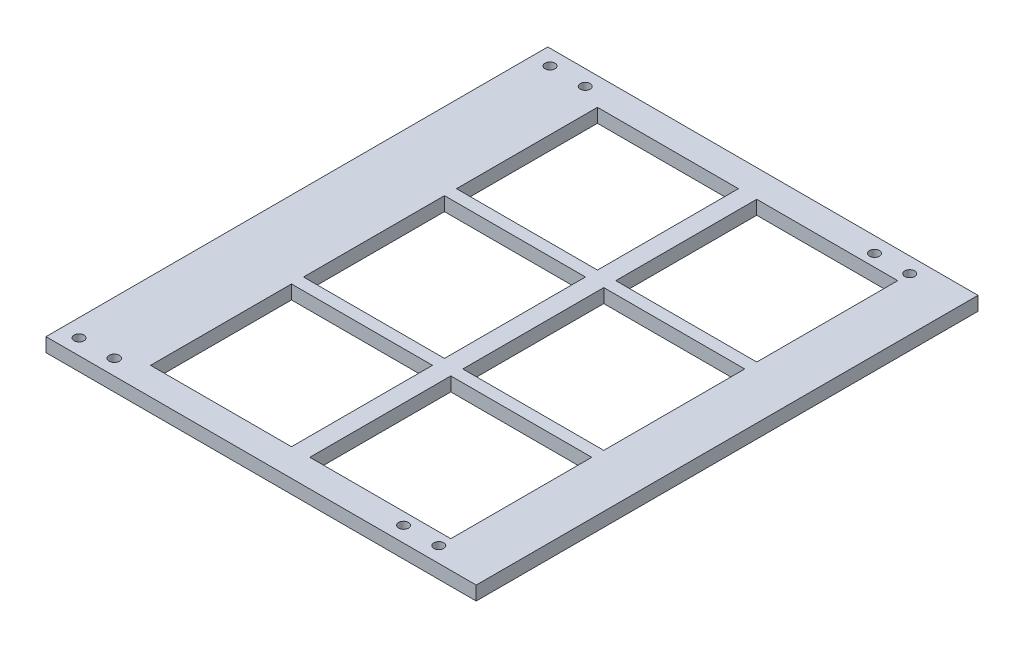
SolidWorks part; units mm, degrees
ref_plane "前视" through (0, 0, 0) normal (0, 0, 1) x (1, 0, 0)
ref_plane "上视" through (0, 0, 0) normal (0, 1, 0) x (1, 0, 0)
ref_plane "右视" through (0, 0, 0) normal (1, 0, 0) x (0, 0, -1)
sketch "Sketch1" plane through (0, 0, 0) normal (0, 1, 0) x (1, 0, 0)
  line L1 (-176.485, 180.84) -> (133.61, 180.84)
  line L2 (-176.485, 180.84) -> (-176.485, -180.84)
  line L3 (-176.485, -180.84) -> (133.61, -180.84)
  line L4 (133.61, 180.84) -> (133.61, -180.84)
  circle A0 centre (-163.785, -169.7275) radius 3.57
  circle A1 centre (-163.785, 169.7275) radius 3.57
  circle A2 centre (70.11, 169.7275) radius 3.57
  circle A3 centre (70.11, -169.7275) radius 3.57
  circle A4 centre (-138.385, 169.7275) radius 3.57
  circle A5 centre (-138.385, -169.7275) radius 3.7
  circle A6 centre (95.51, 169.7275) radius 3.57
  circle A7 centre (95.51, -169.7275) radius 3.57
  point P4 (-163.785, -169.7275)
  point P7 (70.11, -169.7275)
  point P8 (70.11, 169.7275)
  point P9 (-163.785, 169.7275)
  point P17 (-138.385, -169.7275)
  point P18 (-138.385, 169.7275)
  point P23 (95.51, -169.7275)
  point P24 (95.51, 169.7275)
  dimension "D5" = 63.5
  dimension "D7" = 233.895
  dimension "D14" = 7.14
  dimension "D16" = 25.4
  dimension "D1" = 310.095
  dimension "D2" = 361.68
  dimension "D3" = 11.1125
  dimension "D4" = 12.7
  dimension "D6" = 11.1125
  dimension "D8" = 63.5
  dimension "D9" = 11.1125
  dimension "D10" = 12.7
  dimension "D11" = 180.84
  dimension "D12" = 133.61
  dimension "D13" = 25.4
  dimension "D15" = 25.4
  dimension "D17" = 25.4
extrude "Boss-Extrude1" add sketch "Sketch1" along normal blind 10
sketch "Sketch2" plane through (0, 10, 0) normal (0, 1, 0) x (1, 0, 0)
  line L0 (-120.91, 50.8) -> (-19.31, 50.8)
  line L1 (-120.91, 50.8) -> (-120.91, -50.8)
  line L2 (-19.31, 50.8) -> (-19.31, -50.8)
  line L3 (-120.91, -50.8) -> (-19.31, -50.8)
  line L4 (-120.91, 50.8) -> (-19.31, -50.8) construction
  line L5 (-19.31, 50.8) -> (-120.91, -50.8) construction
  circle A1 centre (-163.785, 169.7275) radius 3.57 construction
  point P1 (-70.11, 0)
  dimension "D4" = 0
  dimension "D3" = 93.675
  dimension "D1" = 101.6
  dimension "D2" = 101.6
extrude "Cut-Extrude1" cut sketch "Sketch2" against normal through all
pattern_linear "LPattern1" count 2 spacing 110.265 along (0, 0, -1) of "Cut-Extrude1"
pattern_linear "LPattern2" count 2 spacing 110.265 along (0, 0, 1) of "Cut-Extrude1"
pattern_linear "LPattern3" count 2 spacing 114.82 along (1, 0, 0) of "Cut-Extrude1", "LPattern1", "LPattern2"
